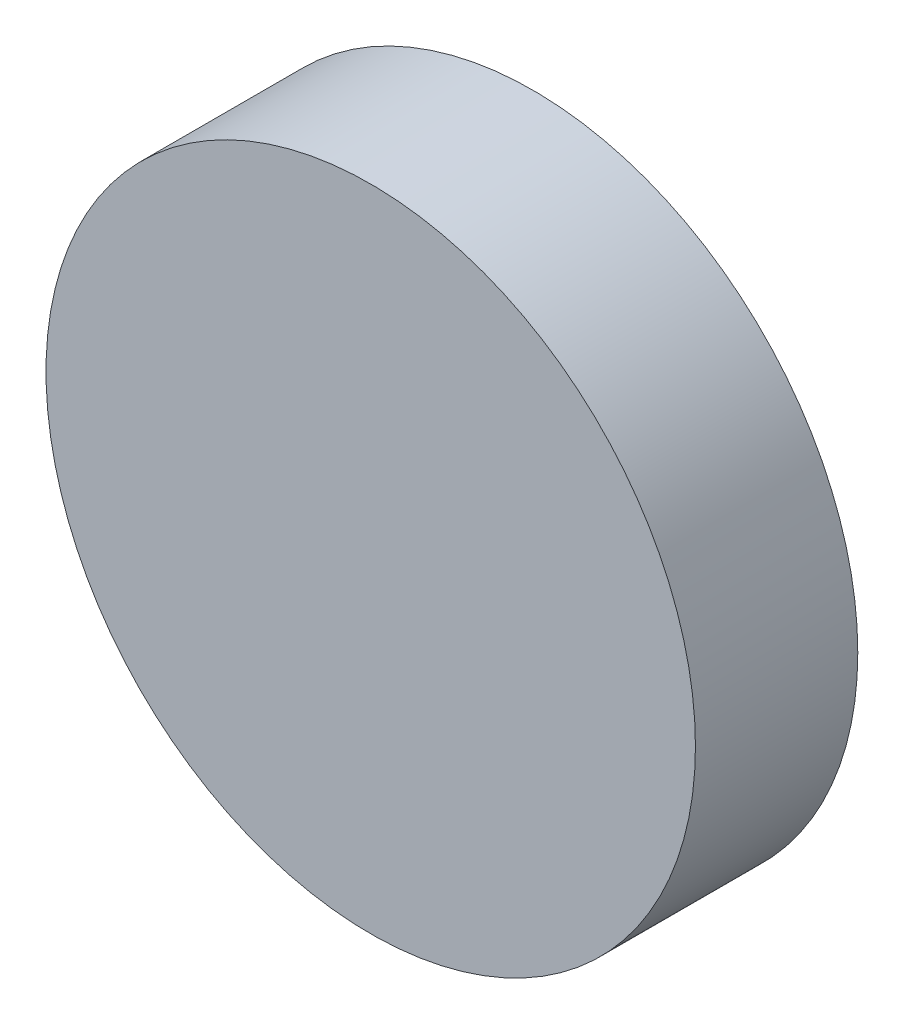
SolidWorks part; units mm, degrees
ref_plane "Front Plane" through (0, 0, 0) normal (0, 0, 1) x (1, 0, 0)
ref_plane "Top Plane" through (0, 0, 0) normal (0, 1, 0) x (1, 0, 0)
ref_plane "Right Plane" through (0, 0, 0) normal (1, 0, 0) x (0, 0, -1)
sketch "Sketch1" plane through (0, 0, 0) normal (0, 0, 1) x (1, 0, 0)
  circle A0 centre (0, 0) radius 25.4
  dimension "D1" = 50.8
extrude "Boss-Extrude1" add sketch "Sketch1" along normal blind 12.7
